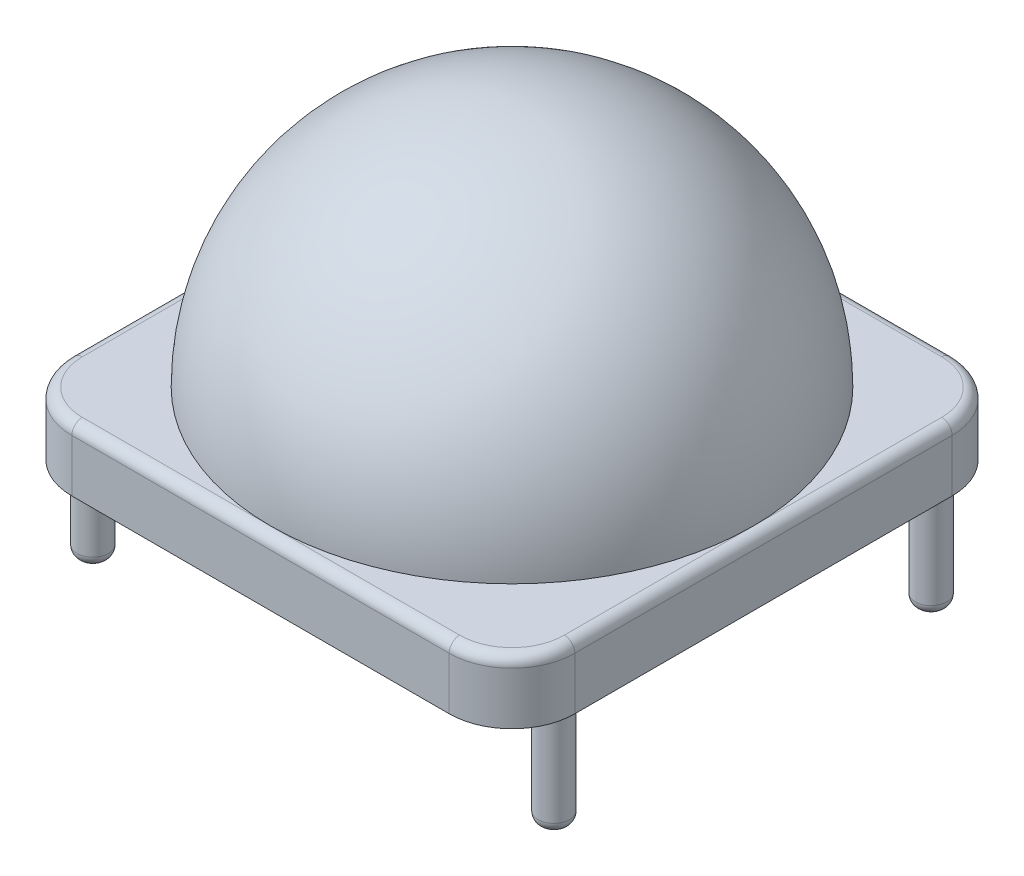
SolidWorks part; units mm, degrees
material "1060 Alloy"
ref_plane "Front" through (0, 0, 0) normal (0, 0, 1) x (1, 0, 0)
ref_plane "Top" through (0, 0, 0) normal (0, 1, 0) x (1, 0, 0)
ref_plane "Right" through (0, 0, 0) normal (1, 0, 0) x (0, 0, -1)
sketch "Sketch1" plane through (0, 0, 0) normal (0, 1, 0) x (1, 0, 0)
  line L1 (-12, -12) -> (12, -12)
  line L2 (-12, -12) -> (-12, 12)
  line L3 (-12, 12) -> (12, 12)
  line L4 (12, -12) -> (12, 12)
  line L5 (-12, -12) -> (12, 12) construction
  line L6 (-12, 12) -> (12, -12) construction
  point P0 (0, 0)
  dimension "D1" = 24
extrude "Boss-Extrude1" add sketch "Sketch1" along normal blind 2 and the other way blind 1
sketch "Sketch2" plane through (0, 0, 0) normal (1, 0, 0) x (0, 0, -1)
  line L0 (-12, 2) -> (12, 2) construction
  line L1 (0, -3.6976) -> (0, 18.9694) construction
  line L2 (0, 2) -> (11.5, 2)
  line L3 (0, 13.5) -> (0, 2)
  arc A0 (0, 13.5) -> (11.5, 2) centre (0, 2) cw
  dimension "D1" = 11.5
revolve "Revolve2" add sketch "Sketch2" angle 360 about L1
fillet "Fillet1" radius 3 4 edges at (-12, 0.5, -12) (-12, 0.5, 12) (12, 0.5, 12) (12, 0.5, -12)
shell "Shell2" thickness 2 removed face at (0, -1, 0)
sketch "Sketch3" plane through (0, -1, 0) normal (0, -1, 0) x (1, 0, 0)
  line L2 (0, 12.0407) -> (0, -12.7161) construction
  line L3 (-13.1845, 0) -> (16.3577, 0) construction
  circle A0 centre (-11, 9) radius 0.75
  circle A1 centre (11, 9) radius 0.75
  circle A2 centre (11, -9) radius 0.75
  circle A3 centre (-11, -9) radius 0.75
  dimension "D1" = 1.5
  dimension "D2" = 11
  dimension "D3" = 9
extrude "Boss-Extrude2" add sketch "Sketch3" along normal blind 5
ref_axis "Axis2" through (0, 50, 0) along (0, -1, 0)
sketch "Sketch7" plane through (0, 0, 0) normal (0, 1, 0) x (1, 0, 0)
  line L1 (3.2361, 1.0515) -> (0, 3.4026)
  line L2 (0, 3.4026) -> (-3.2361, 1.0515)
  line L3 (-3.2361, 1.0515) -> (-2, -2.7528)
  line L4 (-2, -2.7528) -> (2, -2.7528)
  line L5 (2, -2.7528) -> (3.2361, 1.0515)
  circle A0 centre (0, 0) radius 2.7528 construction
  dimension "D1" = 4
extrude "Cut-Extrude4" cut sketch "Sketch7" along normal blind 12
ref_plane "Plane3" through (5.9635, 9.734, 1.9377) normal (0.515, 0.8407, 0.1673) x (0.309, 0, -0.9511)
sketch "Sketch8" plane through (5.9635, 9.734, 1.9377) normal (0.515, 0.8407, 0.1673) x (0.309, 0, -0.9511)
  line L0 (-2, 4.1843) -> (2, 4.1843) construction
  line L1 (4, 0.7202) -> (2, 4.1843)
  line L2 (2, 4.1843) -> (-2, 4.1843)
  line L3 (-2, 4.1843) -> (-4, 0.7202)
  line L5 (-4, 0.7202) -> (-2, -2.7439)
  line L6 (-2, -2.7439) -> (2, -2.7439)
  line L7 (2, -2.7439) -> (4, 0.7202)
  circle A0 centre (0, 0.7202) radius 3.4641 construction
  dimension "D1" = 4
extrude "Cut-Extrude5" cut sketch "Sketch8" against normal blind 5
ref_axis "Axis3" through (0, -50, 0) along (0, 1, 0)
pattern_circular "CirPattern3" count 5 over 288 about axis through (0, -50, 0) along (0, 1, 0) of "Cut-Extrude5"
ref_plane "Plane4" through (-2.3297, 1.1775, -0.757) normal (-0.8572, 0.4332, -0.2785) x (0.309, 0, -0.9511)
ref_plane "Plane5" through (-9.4013, 4.7517, -3.0547) normal (-0.8572, 0.4332, -0.2785) x (0.309, 0, -0.9511)
sketch "Sketch9" plane through (-9.4013, 4.7517, -3.0547) normal (-0.8572, 0.4332, -0.2785) x (0.309, 0, -0.9511)
  line L0 (2.9665, -3.1031) -> (3.4235, -3.9183) construction
  line L1 (3.4482, 0.0192) -> (0, 2.0101)
  line L2 (0, 2.0101) -> (-3.4482, 0.0192)
  line L3 (-3.4482, 0.0192) -> (-3.4482, -3.9624)
  line L4 (-3.4482, -3.9624) -> (0, -5.9533)
  line L5 (0, -5.9533) -> (3.4482, -3.9624)
  line L6 (3.4482, -3.9624) -> (3.4482, 0.0192)
  line L7 (-2.9665, -3.1031) -> (-3.4235, -3.9183) construction
  circle A0 centre (0, -1.9716) radius 3.4482 construction
extrude "Cut-Extrude6" cut sketch "Sketch9" against normal blind 5
pattern_circular "CirPattern5" count 5 over 360 about axis through (0, -50, 0) along (0, 1, 0) of "Cut-Extrude6"
ref_plane "Plane6" through (-9.7323, 4.3707, 3.1622) normal (-0.8746, 0.3928, 0.2842) x (-0.309, 0, -0.9511)
sketch "Sketch10" plane through (-9.7323, 4.3707, 3.1622) normal (-0.8746, 0.3928, 0.2842) x (-0.309, 0, -0.9511)
  line L1 (1.9694, -4.2162) -> (-1.9694, -4.2162) construction
  line L2 (1.999, -4.2162) -> (3.2344, -0.4139)
  line L3 (3.2344, -0.4139) -> (0, 1.936)
  line L4 (0, 1.936) -> (-3.2344, -0.4139)
  line L5 (-3.2344, -0.4139) -> (-1.999, -4.2162)
  line L6 (-1.999, -4.2162) -> (1.999, -4.2162)
  circle A0 centre (0, -1.4648) radius 2.7514 construction
  point P9 (0, -4.2162)
  point P14 (0, -4.2162)
extrude "Cut-Extrude7" cut sketch "Sketch10" against normal blind 5
pattern_circular "CirPattern6" count 5 over 360 about axis through (0, -50, 0) along (0, 1, 0) of "Cut-Extrude7"
sketch "Sketch11" plane through (0, 0, 0) normal (1, 0, 0) x (0, 0, -1)
  line L0 (-3.2625, 2) -> (3.3512, 2)
  line L1 (3.3512, 2) -> (3.3238, 2.9401)
  line L2 (3.3238, 2.9401) -> (-0.0359, 4.7514)
  line L3 (-0.0359, 4.7514) -> (-3.2843, 2.7475)
  line L4 (-3.2843, 2.7475) -> (-3.2625, 2)
  line L5 (-9, 2) -> (9, 2) construction
  line L6 (0.1865, -2.879) -> (3.4349, -0.8751) [skipped]
  line L7 (-3.1731, -1.0677) -> (0.1865, -2.879) [skipped]
  arc A0 (3.2049, 2) -> (-3.0543, 2) centre (0.0753, 0.9362) ccw construction
extrude "Cut-Extrude8" cut sketch "Sketch11" along normal blind 10.5
pattern_circular "CirPattern7" count 10 over 360 about axis through (0, 50, 0) along (0, -1, 0) of "Cut-Extrude8"
fillet "Fillet2" radius 0.5 8 edges at (11.1213, 2, -11.1213) (12, 2, 0) (-12, 2, 0) (-11.1213, 2, -11.1213) (0, 2, -12) (11.1213, 2, 11.1213) (0, 2, 12) (-11.1213, 2, 11.1213)
fillet "Fillet3" radius 0.5 4 edges at (-11, -6, -8.25) (11, -6, -9.75) (11, -6, 9.75) (-11, -6, 8.25)
